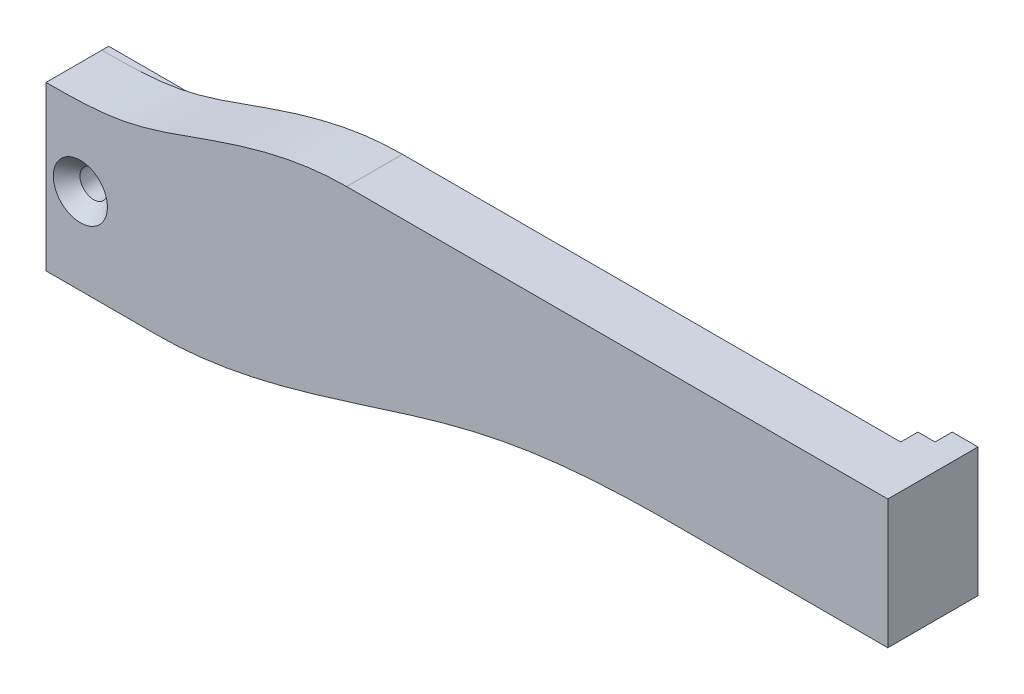
SolidWorks part; units mm, degrees
ref_plane "Front Plane" through (0, 0, 0) normal (0, 0, 1) x (1, 0, 0)
ref_plane "Top Plane" through (0, 0, 0) normal (0, 1, 0) x (1, 0, 0)
ref_plane "Right Plane" through (0, 0, 0) normal (1, 0, 0) x (0, 0, -1)
sketch "Sketch1" plane through (0, 0, 0) normal (0, 0, 1) x (1, 0, 0)
  line L1 (-53.7227, 46.4585) -> (44.2773, 46.4585)
  line L2 (-53.7227, 46.4585) -> (-53.7227, 72.4585)
  line L3 (-53.7227, 72.4585) -> (44.2773, 72.4585)
  line L4 (44.2773, 46.4585) -> (44.2773, 72.4585)
  dimension "D1" = 98
  dimension "D2" = 26
extrude "Boss-Extrude1" add sketch "Sketch1" along normal blind 6.5
sketch "Sketch3" plane through (0, 0, 0) normal (0, 0, -1) x (-1, 0, 0)
  line L0 (-44.2773, 72.4585) -> (-44.2773, 57.4585)
  line L1 (-44.2773, 46.4585) -> (-44.2773, 72.4585) construction
  line L2 (-44.2773, 57.4585) -> (-42.2773, 57.4585)
  line L3 (-42.2773, 57.4585) -> (-42.2773, 70.4585)
  line L4 (-42.2773, 70.4585) -> (-39.2773, 70.4585)
  line L5 (-39.2773, 70.4585) -> (-39.2773, 72.4585)
  line L12 (-39.2773, 72.4585) -> (-44.2773, 72.4585)
  line L21 (53.7227, 46.4585) -> (-44.2773, 46.4585) construction
  dimension "D1" = 26
  dimension "D2" = 2
  dimension "D3" = 2
  dimension "D4" = 5
  dimension "D5" = 11
extrude "Boss-Extrude2" add sketch "Sketch3" along normal blind 2
sketch "Sketch4" plane through (0, 0, 0) normal (0, 0, -1) x (-1, 0, 0)
  line L0 (-44.2773, 57.4585) -> (-19.2773, 57.4585)
  line L1 (-44.2773, 72.4585) -> (-44.2773, 57.4585) construction
  line L2 (53.7227, 46.4585) -> (-44.2773, 46.4585) construction
  line L4 (-44.2773, 57.4585) -> (-42.2773, 57.4585) construction
  line L5 (53.7227, 72.4585) -> (53.7227, 46.4585) construction
  line L6 (-44.2773, 57.4585) -> (-44.2773, 46.4585)
  line L7 (-44.2773, 46.4585) -> (40.7227, 46.4585)
  line L8 (-39.2773, 72.4585) -> (53.7227, 72.4585) construction
  line L9 (18.7227, 72.4585) -> (53.7227, 72.4585)
  line L10 (53.7227, 72.4585) -> (53.7227, 65.4585)
  spline S0 degree 3 poles (-19.2773, 57.4585) (-7.8329, 57.4585) (8.9041, 55.154) (29.5296, 46.4585) (40.7227, 46.4585) knots 0 0 0 0 0.448706 1 1 1 1
  spline S1 degree 3 poles (18.7227, 72.4585) (24.2378, 72.4585) (33.0452, 69.9965) (44.1784, 65.5489) (50.9611, 65.4585) (53.7227, 65.4585) knots 0 0 0 0 0.451492 0.761184 1 1 1 1
  point P13 (23.2727, 50.8608)
  point P14 (34.1121, 47.0592)
  point P17 (36.9319, 73.6681)
  point P18 (7.9704, 54.1036)
  point P21 (24.7803, 74.903)
  point P25 (36.2431, 68.7852)
  point P27 (24.3295, 73.1643)
  point P28 (24.6515, 73.5507)
  point P29 (26.0214, 71.8374)
  point P30 (40.0328, 66.7778)
  point P31 (26.3185, 72.257)
  point P32 (26.5389, 69.5821)
  point P33 (44.3062, 66.3979)
  point P34 (34.5688, 69.2129)
  point P35 (45.183, 65.9825)
  dimension "D2" = 13
  dimension "D4" = 35
  dimension "D1" = 25
  dimension "D3" = 19
extrude "Cut-Extrude2" cut sketch "Sketch4" against normal through all and the other way through all
sketch "Sketch5" plane through (0, 0, 0) normal (0, 0, -1) x (-1, 0, 0)
  line L0 (43.2227, 46.4585) -> (40.7227, 46.4585)
  line L1 (40.7227, 64.9585) -> (41.2227, 65.4585)
  line L2 (53.7227, 46.4585) -> (40.7227, 46.4585) construction
  line L3 (40.7227, 46.4585) -> (40.7227, 64.9585)
  line L4 (41.2227, 65.4585) -> (53.7227, 65.4585)
  line L5 (53.7227, 65.4585) -> (53.7227, 46.4585) construction
  line L6 (53.7227, 65.4585) -> (53.7227, 62.9585)
  line L7 (53.7227, 62.9585) -> (44.1227, 62.9585)
  line L8 (43.2227, 62.0585) -> (43.2227, 46.4585)
  arc A0 (44.1227, 62.9585) -> (43.2227, 62.0585) centre (44.1227, 62.0585) ccw
  point P5 (40.7227, 65.4585)
  dimension "D5" = 0.9
  dimension "D1" = 13
  dimension "D2" = 19
  dimension "D3" = 2.5
  dimension "D4" = 2.5
extrude "Boss-Extrude3" add sketch "Sketch5" along normal blind 0.8
sketch "Sketch6" plane through (0, 0, -2) normal (0, 0, -1) x (-1, 0, 0)
  line L0 (-39.2773, 72.4585) -> (-44.2773, 72.4585) construction
  line L1 (-44.2773, 72.4585) -> (-41.2773, 72.4585)
  line L2 (-44.2773, 72.4585) -> (-44.2773, 57.4585)
  line L3 (-44.2773, 57.4585) -> (-41.2773, 57.4585)
  line L4 (-41.2773, 72.4585) -> (-41.2773, 57.4585)
  line L5 (-19.2773, 57.4585) -> (-42.2773, 57.4585) construction
  line L6 (-44.2773, 57.4585) -> (-44.2773, 72.4585) construction
  dimension "D1" = 3
extrude "Boss-Extrude4" add sketch "Sketch6" along normal blind 2
chamfer "Chamfer1" distance 0.8 angle 45 1 edges at (42.2773, 63.9585, -2)
hole_wizard "CSK for M3 Flat Head Machine Screw1" positions "Sketch10" profile "Sketch11" countersink size "M3" standard "ANSI Metric" end condition through all
sketch "Sketch10" plane through (0, 0, 6.5) normal (0, 0, 1) x (1, 0, 0)
  point P0 (-49.7227, 56.4585)
sketch "Sketch11" plane through (-49.7227, 56.4585, 6.5) normal (1, 0, 0) x (0, -1, 0)
  line L0 (0, 0) -> (0, 10.5)
  line L1 (0, 10.5) -> (1.6, 10.5)
  line L2 (1.6, 10.5) -> (1.6, 1.55)
  line L3 (1.6, 1.55) -> (3.15, 0)
  line L5 (3.15, 0) -> (0, 0)
  line L6 (-1.6, 1.55) -> (-3.15, 0) construction
  line L11 (0, -6.35) -> (0, 107.95) construction
  dimension "Thru Hole Dia." = 3.2
  dimension "Thru Hole Depth" = 10.5
  dimension "Near C'Sink Dia." = 6.3
  dimension "Near C'Sink Angle" = 90
sketch "Sketch12" plane through (0, 0, 0) normal (0, 0, -1) x (-1, 0, 0)
  circle A0 centre (19.6477, 68.8835) radius 2
  dimension "D1" = 4
extrude "Cut-Extrude3" cut sketch "Sketch12" against normal blind 5
